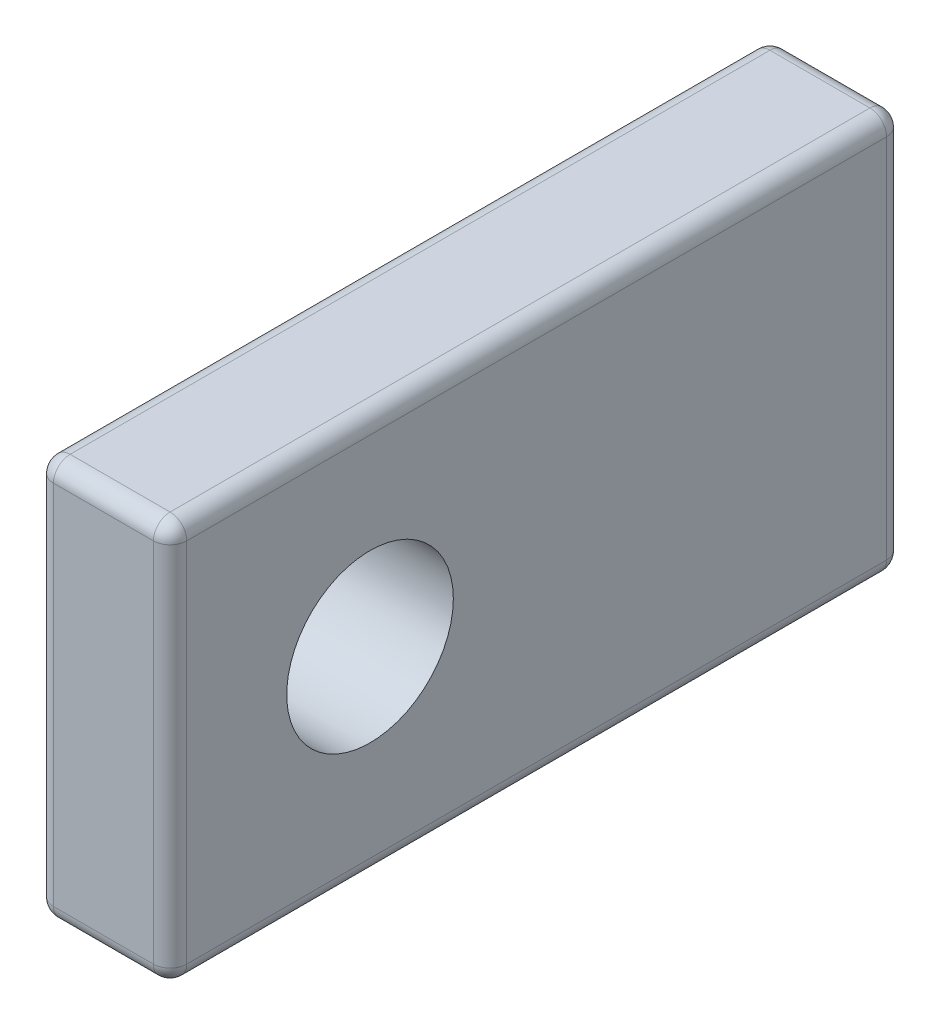
SolidWorks part; units mm, degrees
material "Alloy Steel"
ref_plane "Front Plane" through (0, 0, 0) normal (0, 0, 1) x (1, 0, 0)
ref_plane "Top Plane" through (0, 0, 0) normal (0, 1, 0) x (1, 0, 0)
ref_plane "Right Plane" through (0, 0, 0) normal (1, 0, 0) x (0, 0, -1)
sketch "Sketch2" plane through (0, 0, 0) normal (1, 0, 0) x (0, 0, -1)
  line L1 (-9.525, 9.525) -> (25.4, 9.525)
  line L2 (-9.525, 9.525) -> (-9.525, -9.525)
  line L3 (-9.525, -9.525) -> (25.4, -9.525)
  line L4 (25.4, 9.525) -> (25.4, -9.525)
  circle A0 centre (0, 0) radius 3.9688
  dimension "D1" = 7.9375
  dimension "D2" = 9.525
  dimension "D3" = 34.925
  dimension "D4" = 19.05
  dimension "D5" = 9.525
extrude "Boss-Extrude1" add sketch "Sketch2" along normal mid plane 6.35
fillet "Fillet1" radius 0.7937 12 edges at (-3.175, -9.525, -7.9375) (0, -9.525, -25.4) (0, 9.525, -25.4) (-3.175, 9.525, -7.9375) (-3.175, 0, -25.4) (3.175, 0, -25.4) (3.175, -9.525, -7.9375) (0, -9.525, 9.525) (-3.175, 0, 9.525) (3.175, 0, 9.525) (0, 9.525, 9.525) (3.175, 9.525, -7.9375)
